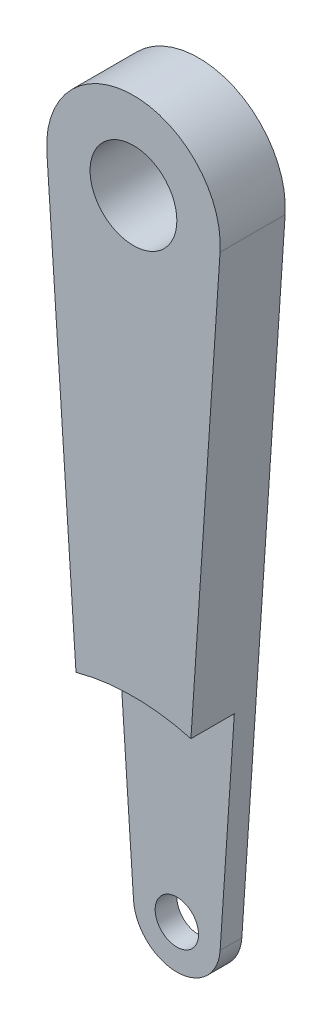
SolidWorks part; units mm, degrees
ref_plane "Front Plane" through (0, 0, 0) normal (0, 0, 1) x (1, 0, 0)
ref_plane "Top Plane" through (0, 0, 0) normal (0, 1, 0) x (1, 0, 0)
ref_plane "Right Plane" through (0, 0, 0) normal (1, 0, 0) x (0, 0, -1)
sketch "Sketch1" plane through (0, 0, 0) normal (0, 0, 1) x (1, 0, 0)
  line L0 (0, 0) -> (0, 50) construction
  line L1 (0, 50) -> (0, 20) construction
  line L2 (1.9956, 19.8667) -> (3.9911, 49.7333)
  line L3 (-1.9956, 19.8667) -> (-3.9911, 49.7333)
  circle A0 centre (0, 50) radius 2
  arc A1 (3.9911, 49.7333) -> (-3.9911, 49.7333) centre (0, 50) ccw
  circle A2 centre (0, 20) radius 1
  arc A3 (-1.9956, 19.8667) -> (1.9956, 19.8667) centre (0, 20) ccw
  point P12 (0, 19.8667)
  dimension "D2" = 4
  dimension "D3" = 8
  dimension "D5" = 2
  dimension "D6" = 4
  dimension "D1" = 50
  dimension "D4" = 30
extrude "Boss-Extrude1" add sketch "Sketch1" along normal blind 3
ref_axis "Axis2" through (0, 50, 3) along (0, 0, -1)
sketch "Sketch2" plane through (0, 0, 3) normal (0, 0, 1) x (1, 0, 0)
  circle A0 centre (0, 20) radius 10
  dimension "D1" = 20
extrude "Cut-Extrude1" cut sketch "Sketch2" against normal blind 2
